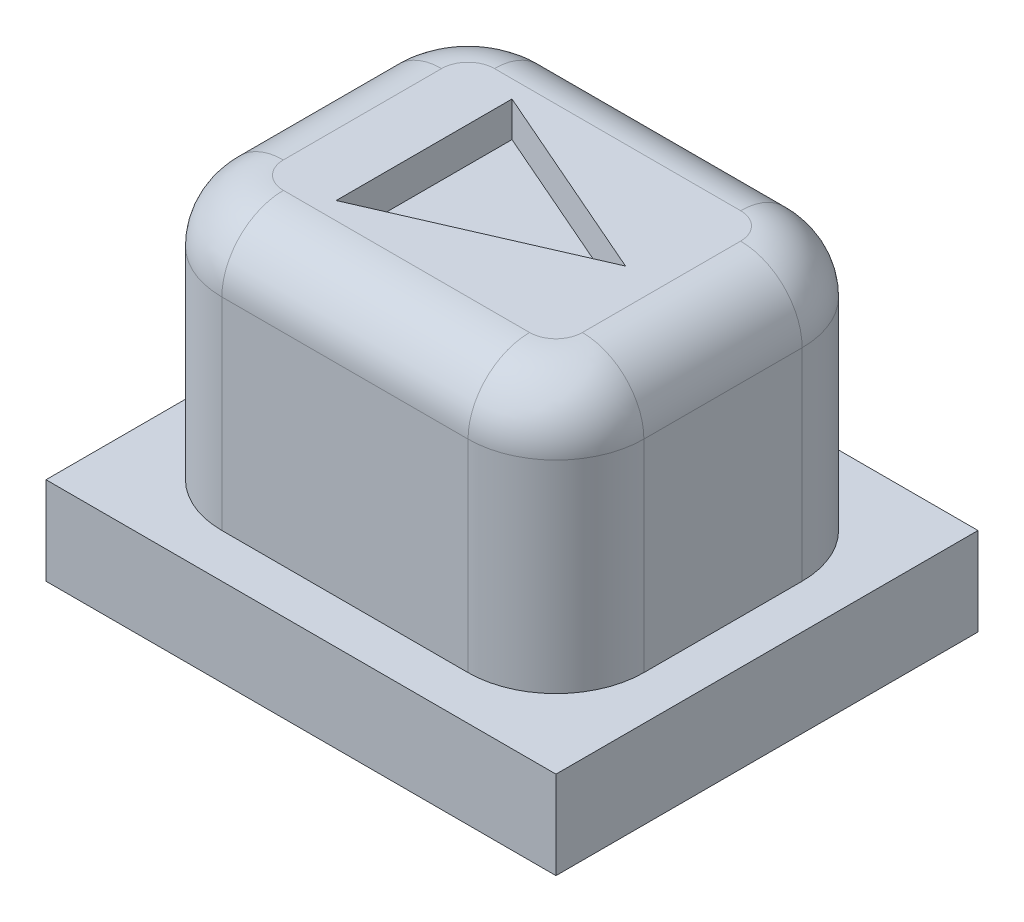
SolidWorks part; units mm, degrees
ref_plane "前视基准面" through (0, 0, 0) normal (0, 0, 1) x (1, 0, 0)
ref_plane "上视基准面" through (0, 0, 0) normal (0, 1, 0) x (1, 0, 0)
ref_plane "右视基准面" through (0, 0, 0) normal (1, 0, 0) x (0, 0, -1)
sketch "草图1" plane through (0, 0, 0) normal (0, 1, 0) x (1, 0, 0)
  line L1 (-1.4, -1.9) -> (1.4, -1.9)
  line L2 (-2.4, -0.9) -> (-2.4, 0.9)
  line L3 (-1.4, 1.9) -> (1.4, 1.9)
  line L4 (2.4, -0.9) -> (2.4, 0.9)
  line L5 (-2.4, -1.9) -> (2.4, 1.9) construction
  line L6 (-2.4, 1.9) -> (2.4, -1.9) construction
  arc A0 (1.4, -1.9) -> (2.4, -0.9) centre (1.4, -0.9) ccw
  arc A1 (-1.4, -1.9) -> (-2.4, -0.9) centre (-1.4, -0.9) cw
  arc A2 (1.4, 1.9) -> (2.4, 0.9) centre (1.4, 0.9) cw
  arc A3 (-2.4, 0.9) -> (-1.4, 1.9) centre (-1.4, 0.9) cw
  point P0 (0, 0)
  dimension "D3" = 1
  dimension "D1" = 4.8
  dimension "D2" = 3.8
extrude "按钮柱体" add sketch "草图1" along normal blind 3
sketch "草图2" plane through (0, 0, 0) normal (0, -1, 0) x (1, 0, 0)
  line L1 (-2.9, -2.4) -> (2.9, -2.4)
  line L2 (-2.9, -2.4) -> (-2.9, 2.4)
  line L3 (-2.9, 2.4) -> (2.9, 2.4)
  line L4 (2.9, -2.4) -> (2.9, 2.4)
  line L5 (-2.9, -2.4) -> (2.9, 2.4) construction
  line L6 (-2.9, 2.4) -> (2.9, -2.4) construction
  point P0 (0, 0)
  dimension "D1" = 5.8
  dimension "D2" = 4.8
extrude "按钮底座" add sketch "草图2" along normal blind 1
sketch "草图3" plane through (0, -1, 0) normal (0, -1, 0) x (1, 0, 0)
  line L1 (-0.75, -1.25) -> (0.75, -1.25)
  line L2 (-1.75, -0.25) -> (-1.75, 0.25)
  line L3 (-0.75, 1.25) -> (0.75, 1.25)
  line L4 (1.75, -0.25) -> (1.75, 0.25)
  line L5 (-1.75, -1.25) -> (1.75, 1.25) construction
  line L6 (-1.75, 1.25) -> (1.75, -1.25) construction
  arc A1 (0.75, 1.25) -> (1.75, 0.25) centre (0.75, 0.25) cw
  arc A2 (-0.75, -1.25) -> (-1.75, -0.25) centre (-0.75, -0.25) cw
  arc A3 (0.75, -1.25) -> (1.75, -0.25) centre (0.75, -0.25) ccw
  arc A4 (-1.75, 0.25) -> (-0.75, 1.25) centre (-0.75, 0.25) cw
  point P0 (0, 0)
  dimension "D1" = 3.5
  dimension "D3" = 1
  dimension "D2" = 2.5
extrude "底部凹槽" cut sketch "草图3" against normal blind 1
sketch "草图4" plane through (0, 3, 0) normal (0, 1, 0) x (1, 0, 0)
  line L0 (-1, 1) -> (-1, -1)
  line L1 (0, 0) -> (1.2725, 0) construction
  line L2 (-1, 1) -> (1.2913, 0)
  line L3 (1.2913, 0) -> (-1, -1)
  point P3 (-1, 0)
  dimension "D1" = 2
  dimension "D2" = 2.5
  dimension "D3" = 1
extrude "按钮图标" cut sketch "草图4" against normal blind 0.4
fillet "圆角1" radius 0.7 8 edges at (2.1071, 3, -1.6071) (2.4, 3, 0) (2.1071, 3, 1.6071) (0, 3, 1.9) (-2.1071, 3, 1.6071) (-2.4, 3, 0) (-2.1071, 3, -1.6071) (0, 3, -1.9)
